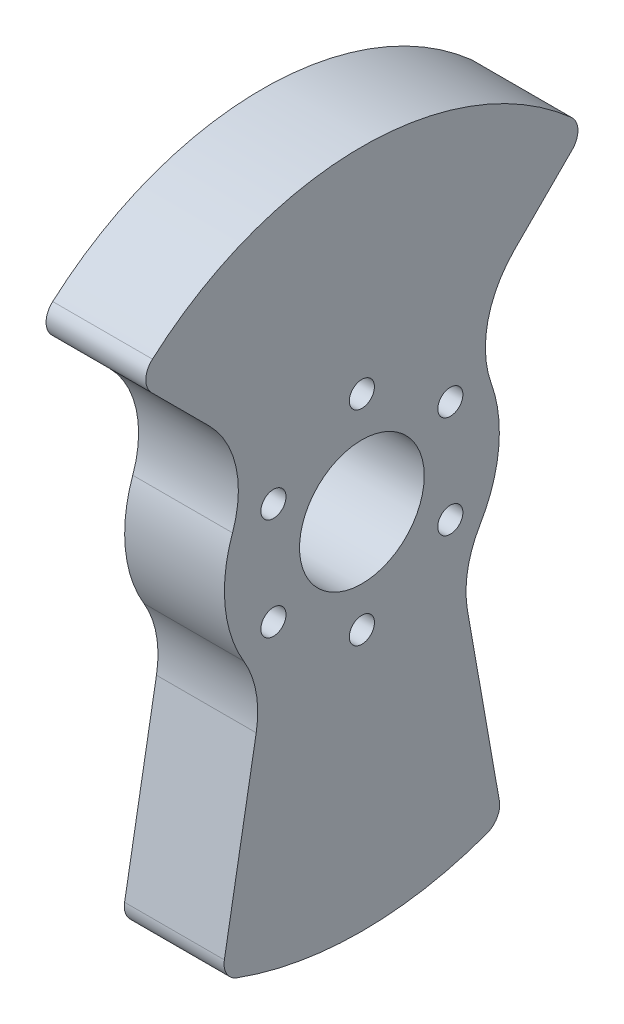
SolidWorks part; units mm, degrees
material "Alloy Steel"
ref_plane "Front Plane" through (0, 0, 0) normal (0, 0, 1) x (1, 0, 0)
ref_plane "Top Plane" through (0, 0, 0) normal (0, 1, 0) x (1, 0, 0)
ref_plane "Right Plane" through (0, 0, 0) normal (1, 0, 0) x (0, 0, -1)
other "Center of Mass"
sketch "Sketch1" plane through (0, 0, 0) normal (1, 0, 0) x (0, 0, -1)
  line L0 (-35.7256, -85.3225) -> (-25, -24.4949)
  line L1 (0, 0) -> (0, 80.51) construction
  line L2 (35.7256, -85.3225) -> (25, -24.4949)
  line L3 (-57.1812, 56.6761) -> (-25, 24.4949)
  line L4 (57.1812, 56.6761) -> (25, 24.4949)
  line L6 (-76.2, -152.4) -> (76.2, -152.4) construction
  line L7 (-76.2, -152.4) -> (-76.2, 152.4) construction
  line L8 (-76.2, 152.4) -> (76.2, 152.4) construction
  line L9 (76.2, -152.4) -> (76.2, 152.4) construction
  line L10 (-76.2, -152.4) -> (76.2, 152.4) construction
  line L11 (-76.2, 152.4) -> (76.2, -152.4) construction
  circle A0 centre (0, 0) radius 15.875
  arc A1 (-35.7256, -85.3225) -> (35.7256, -85.3225) centre (0, 0) ccw
  arc A2 (-57.1812, 56.6761) -> (57.1812, 56.6761) centre (0, 0) cw
  arc A3 (-25, 24.4949) -> (-25, -24.4949) centre (0, 0) ccw
  arc A4 (25, -24.4949) -> (25, 24.4949) centre (0, 0) ccw
  point P15 (0, 0)
  dimension "D1" = 31.75
  dimension "D2" = 70
  dimension "D3" = 92.5
  dimension "D4" = 80.51
  dimension "D6" = 90
  dimension "D9" = 152.4
  dimension "D5" = 20
  dimension "D7" = 50
  dimension "D8" = 304.8
extrude "Boss-Extrude1" add sketch "Sketch1" along normal mid plane 25.4 contours A0 A2 L3 A3 L0 A1 L2 A4 L4 region at (0, -55.2688, 28.3204)
fillet "Fillet2" radius 25.4 4 edges at (0, -24.4949, 25) (0, 24.4949, 25) (0, -24.4949, -25) (0, 24.4949, -25)
fillet "Fillet3" radius 5 4 edges at (0, -85.3225, 35.7256) (0, 56.6761, 57.1812) (0, -85.3225, -35.7256) (0, 56.6761, -57.1812)
sketch "Sketch2" plane through (0, 0, 0) normal (1, 0, 0) x (0, 0, -1)
  point P0 (0, -26)
  point P4 (-22.5167, -13)
  point P5 (-22.5167, 13)
  point P6 (0, 26)
  point P7 (22.5167, 13)
  point P8 (22.5167, -13)
  point P9 (0, 0)
  dimension "D2" = 52
  dimension "D1" = 6
hole_wizard "M6 Clearance Hole1" positions "Sketch3" profile "Sketch4" hole size "M6" standard "ANSI Metric" end condition up to next
sketch "Sketch3" plane through (-12.7, 0, 0) normal (-1, 0, 0) x (0, 0, 1)
  point P0 (-22.5167, 13)
  point P3 (0, 26)
  point P6 (22.5167, 13)
  point P9 (22.5167, -13)
  point P12 (0, -26)
  point P15 (-22.5167, -13)
sketch "Sketch4" plane through (-12.7, 13, -22.5167) normal (0, 1, 0) x (0, 0, 1)
  line L0 (0, 0) -> (0, 25.4)
  line L1 (0, 25.4) -> (3.2, 25.4)
  line L2 (3.2, 25.4) -> (3.2, 0)
  line L5 (3.2, 0) -> (0, 0)
  line L11 (0, -6.35) -> (0, 107.95) construction
  dimension "Thru Hole Dia." = 6.4
  dimension "Thru Hole Depth" = 25.4
